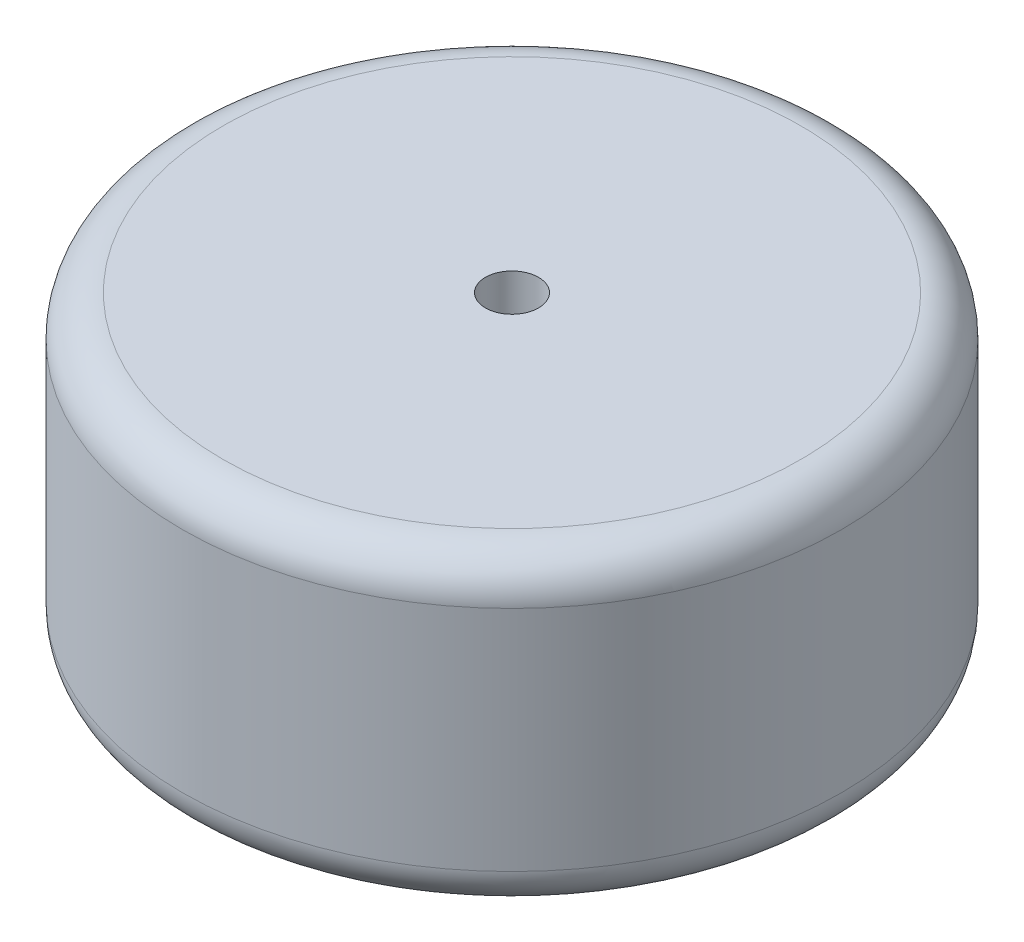
SolidWorks part; units mm, degrees
ref_plane "Front Plane" through (0, 0, 0) normal (0, 0, 1) x (1, 0, 0)
ref_plane "Top Plane" through (0, 0, 0) normal (0, 1, 0) x (1, 0, 0)
ref_plane "Right Plane" through (0, 0, 0) normal (1, 0, 0) x (0, 0, -1)
sketch "Sketch1" plane through (0, 0, 0) normal (0, 1, 0) x (1, 0, 0)
  circle A0 centre (0, 0) radius 40.64
  point P3 (0, 0)
  dimension "D1" = 81.28
extrude "Boss-Extrude1" add sketch "Sketch1" along normal blind 38.1
fillet "Fillet1" radius 5 2 edges at (0, 0, 40.64) (0, 38.1, 40.64)
sketch "Sketch2" plane through (0, 0, 0) normal (0, -1, 0) x (1, 0, 0)
  circle A0 centre (0, 0) radius 3.275
  point P3 (0, 0)
  point P4 (1.587, 0)
  point P5 (-6.0366, -4.5043)
  point P6 (0, 0)
  dimension "D1" = 6.55
extrude "Cut-Extrude1" cut sketch "Sketch2" against normal through all
